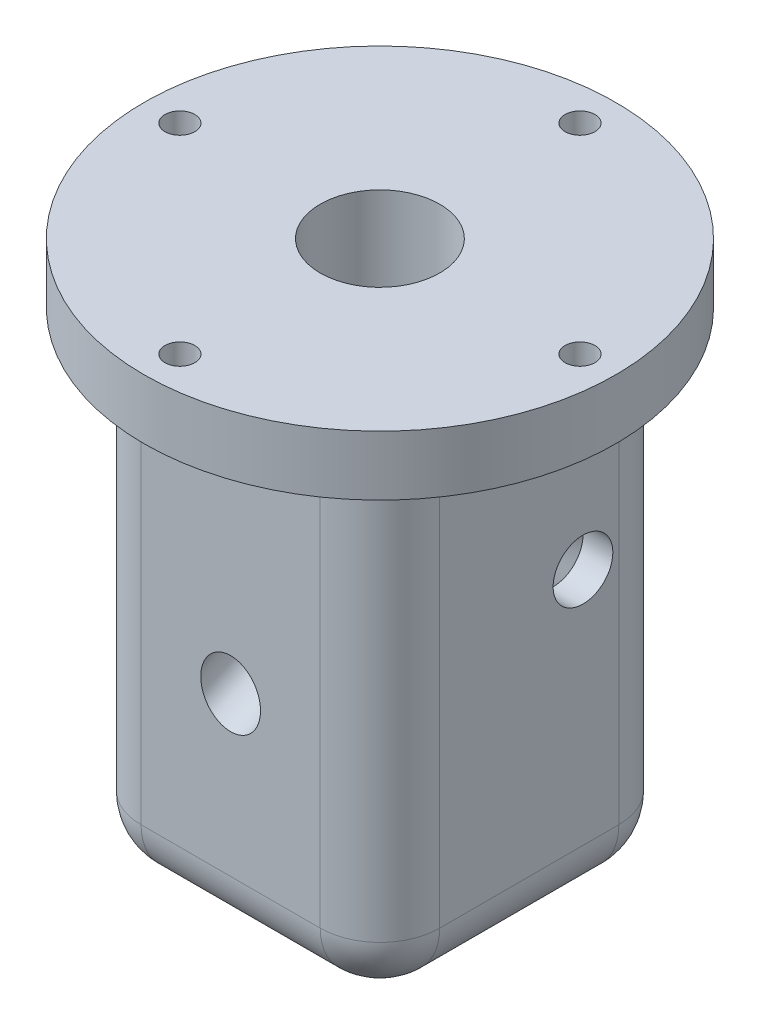
SolidWorks part; units mm, degrees
material "AISI 316 Annealed Stainless Steel Bar (SS)"
ref_plane "Front Plane" through (0, 0, 0) normal (0, 0, 1) x (1, 0, 0)
ref_plane "Top Plane" through (0, 0, 0) normal (0, 1, 0) x (1, 0, 0)
ref_plane "Right Plane" through (0, 0, 0) normal (1, 0, 0) x (0, 0, -1)
sketch "Sketch1" plane through (0, 0, 0) normal (0, 1, 0) x (1, 0, 0)
  line L1 (-15.875, 15.875) -> (15.875, 15.875)
  line L2 (-15.875, 15.875) -> (-15.875, -15.875)
  line L3 (-15.875, -15.875) -> (15.875, -15.875)
  line L4 (15.875, 15.875) -> (15.875, -15.875)
  line L5 (-15.875, 15.875) -> (15.875, -15.875) construction
  line L6 (-15.875, -15.875) -> (15.875, 15.875) construction
  point P0 (0, 0)
  dimension "D1" = 31.75
  dimension "D2" = 31.75
extrude "Stock" add sketch "Sketch1" along normal blind 50.8
sketch "Sketch5" plane through (0, 50.8, 0) normal (0, 1, 0) x (1, 0, 0)
  point P0 (0, 0)
hole_wizard "SP TAP" positions "Sketch5" profile "Sketch6" hole size "50 UNM" standard "ANSI Inch"
sketch "Sketch6" plane through (0, 50.8, 0) normal (1, 0, 0) x (0, 0, 1)
  line L0 (0, 0) -> (0, 36.8355)
  line L1 (0, 36.8355) -> (6.35, 33.02)
  line L2 (6.35, 33.02) -> (6.35, 0)
  line L5 (6.35, 0) -> (0, 0)
  line L10 (0, 36.8355) -> (-6.35, 33.02) construction
  line L11 (0, -6.35) -> (0, 107.95) construction
  dimension "Hole Dia." = 12.7
  dimension "Hole Depth" = 33.02
  dimension "Drill Angle" = 118
sketch "Sketch7" plane through (0, 0, 0) normal (0, 0, 1) x (1, 0, 0)
  line L0 (0, 17.41) -> (-34.9329, 17.41) construction
  line L1 (-34.9329, 17.41) -> (37.6053, 17.41) construction
  line L2 (37.6053, 17.41) -> (0, 17.41) construction
  line L3 (0, 17.41) -> (0, 34.2083) construction
  line L4 (0, 34.2083) -> (0, -2.3153) construction
  dimension "D1" = 17.41
ref_plane "Plane1" through (0, 3.1095, 6.6684) normal (0, 0.4226, 0.9063) x (1, 0, 0)
ref_plane "Plane2" through (0, 3.1095, -6.6684) normal (0, 0.4226, -0.9063) x (1, 0, 0)
ref_plane "Plane3" through (0, -14.0657, 30.1639) normal (0, 0.4226, -0.9063) x (1, 0, 0)
ref_plane "Plane4" through (0, -14.0657, -30.1639) normal (0, 0.4226, 0.9063) x (1, 0, 0)
sketch "Sketch9" plane through (0, -14.0657, -30.1639) normal (0, 0.4226, 0.9063) x (1, 0, 0)
  point P0 (0, 21.9666)
hole_wizard "#47 (0.0785) GOx Orfice" positions "Sketch9" profile "Sketch11" hole size "#47" standard "ANSI Inch" end condition up to next
sketch "Sketch11" plane through (0, 5.8428, -39.4474) normal (1, 0, 0) x (0, 0.9063, -0.4226)
  line L0 (0, 0) -> (0, 36.519)
  line L1 (0, 36.519) -> (0.9969, 36.519)
  line L2 (0.9969, 36.519) -> (0.9969, 0.635)
  line L3 (0.9969, 0.635) -> (1.632, 0)
  line L5 (1.632, 0) -> (0, 0)
  line L6 (-0.9969, 0.635) -> (-1.632, 0) construction
  line L11 (0, -6.35) -> (0, 107.95) construction
  dimension "Thru Hole Dia." = 1.9939
  dimension "Thru Hole Depth" = 36.519
  dimension "Near C'Sink Dia." = 3.2639
  dimension "Near C'Sink Angle" = 90
mirror "Second GOx Orfice" about plane through (0, 0, 0) normal (0, 0, 1) of "#47 (0.0785) GOx Orfice"
sketch "Centerline Fuel" plane through (15.875, 0, 0) normal (1, 0, 0) x (0, 0, -1)
  line L0 (0, 50.8) -> (0, 0) construction
  line L1 (-15.875, 50.8) -> (15.875, 50.8) construction
sketch "Kerosene Orfice Position" plane through (15.875, 0, 0) normal (1, 0, 0) x (0, 0, -1)
  line L0 (0, 0) -> (0, 25.4) construction
  line L1 (0, 50.8) -> (0, 0) construction
  line L2 (0, 25.4) -> (5.715, 25.4) construction
  dimension "D1" = 25.4
  dimension "D2" = 5.715
sketch "Sketch23" plane through (15.875, 0, 0) normal (1, 0, 0) x (0, 0, -1)
  point P0 (5.715, 25.4)
hole_wizard "#65 (0.035) Diameter Hole2" positions "Sketch23" profile "Sketch24" hole size "#65" standard "ANSI Inch" end condition up to next
sketch "Sketch24" plane through (15.875, 25.4, -5.715) normal (0, 1, 0) x (0, 0, -1)
  line L0 (0, 0) -> (0, 13.1071)
  line L1 (0, 13.1071) -> (0.4445, 13.1071)
  line L2 (0.4445, 13.1071) -> (0.4445, 0)
  line L5 (0.4445, 0) -> (0, 0)
  line L11 (0, -6.35) -> (0, 107.95) construction
  dimension "Thru Hole Dia." = 0.889
  dimension "Thru Hole Depth" = 13.1071
sketch "Sketch25" plane through (0, 0, 0) normal (0, -1, 0) x (-1, 0, 0)
  line L1 (15.875, 15.875) -> (-15.875, 15.875)
  line L2 (15.875, 15.875) -> (15.875, -15.875)
  line L3 (15.875, -15.875) -> (-15.875, -15.875)
  line L4 (-15.875, 15.875) -> (-15.875, -15.875)
  line L5 (0, -15.875) -> (0, 15.875) construction
  line L6 (15.875, 0) -> (-15.875, 0) construction
  point P0 (0, 0)
extrude "Boss-Extrude1" add sketch "Sketch25" along normal blind 6.35
sketch "Sketch27" plane through (0, -6.35, 0) normal (0, -1, 0) x (-1, 0, 0)
  point P0 (0, 0)
hole_wizard "M14 Tapped Hole1" positions "Sketch27" profile "Sketch29" tap size "M14" standard "ISO"
sketch "Sketch29" plane through (0, -6.35, 0) normal (1, 0, 0) x (0, 0, -1)
  line L0 (0, 0) -> (0, 22.6552)
  line L1 (0, 22.6552) -> (6, 19.05)
  line L2 (6, 19.05) -> (6, 1.025)
  line L3 (6, 1.025) -> (7.025, 0)
  line L5 (7.025, 0) -> (0, 0)
  line L6 (-6, 1.025) -> (-7.025, 0) construction
  line L10 (0, 22.6552) -> (-6, 19.05) construction
  line L11 (0, -6.35) -> (0, 107.95) construction
  dimension "Tap Drill Dia." = 12
  dimension "Tap Drill Depth" = 19.05
  dimension "Near C'Sink Dia." = 14.05
  dimension "Near C'Sink Angle" = 90
  dimension "Drill Angle" = 118
cosmetic thread "Hole Thread1" parameters "D1"=19.05, "D2"=14
sketch "Sketch30" plane through (0, -6.35, 0) normal (0, -1, 0) x (-1, 0, 0)
  circle A0 centre (0, 0) radius 6.0198
  dimension "D1" = 12.0396
extrude "Cut-Extrude1" cut sketch "Sketch30" against normal through all
sketch "Sketch31" plane through (0, 50.8, 0) normal (0, 1, 0) x (1, 0, 0)
  line L1 (-15.875, -15.875) -> (15.875, -15.875)
  line L2 (-15.875, -15.875) -> (-15.875, 15.875)
  line L3 (-15.875, 15.875) -> (15.875, 15.875)
  line L4 (15.875, -15.875) -> (15.875, 15.875)
  line L5 (0, 15.875) -> (0, -15.875) construction
  line L6 (-15.875, 0) -> (15.875, 0) construction
  circle A0 centre (0, 0) radius 21.2725 construction
  circle A1 centre (21.2725, 0) radius 3.5687 construction
  circle A2 centre (0, 0) radius 25.0825
  circle A3 centre (21.2725, 0) radius 1.5875
  circle A7 centre (0, -21.2725) radius 1.5875
  circle A8 centre (-21.2725, 0) radius 1.5875
  circle A9 centre (0, 21.2725) radius 1.5875
  point P22 (1.5875, 1.5875)
  point P23 (0, 0)
  dimension "D1" = 5.3975
  dimension "D2" = 3.81
  dimension "D3" = 3.175
  dimension "D4" = 7.1374
  dimension "D5" = 4
extrude "Boss-Extrude2" add sketch "Sketch31" against normal blind 6.35
sketch "Sketch33" plane through (15.875, 0, 0) normal (1, 0, 0) x (0, 0, -1)
  point P0 (5.715, 25.4)
hole_wizard "1/4 (0.25) Diameter Hole1" positions "Sketch33" profile "Sketch34" hole size "1/4" standard "ANSI Inch"
sketch "Sketch34" plane through (15.875, 25.4, -5.715) normal (0, 1, 0) x (0, 0, -1)
  line L0 (0, 0) -> (0, 5.0827)
  line L1 (0, 5.0827) -> (3.175, 3.175)
  line L2 (3.175, 3.175) -> (3.175, 0)
  line L5 (3.175, 0) -> (0, 0)
  line L10 (0, 5.0827) -> (-3.175, 3.175) construction
  line L11 (0, -6.35) -> (0, 107.95) construction
  dimension "Hole Dia." = 6.35
  dimension "Hole Depth" = 3.175
  dimension "Drill Angle" = 118
sketch "Sketch35" plane through (0, 0, 0) normal (1, 0, 0) x (0, 0, -1)
  line L0 (6.35, 21.2764) -> (15.875, 21.2764) construction
  line L1 (15.875, 44.45) -> (15.875, -6.35) construction
  line L2 (15.875, 21.2764) -> (15.875, 16.8348) construction
  line L3 (15.875, 15.7348) -> (15.875, 17.9348) construction
  line L4 (15.875, 16.8348) -> (6.35, 21.2764) construction
  line L5 (15.875, 19.0556) -> (11.1125, 19.0556) construction
  line L6 (11.1125, 19.0556) -> (11.4997, 15.3718)
  line L7 (11.4997, 15.3718) -> (19.7602, 11.5199)
  line L8 (19.7602, 11.5199) -> (21.102, 14.3974)
  line L9 (15.875, 16.8348) -> (21.102, 14.3974)
  line L10 (11.1125, 19.0556) -> (15.875, 16.8348)
  dimension "D2" = 59
  dimension "D1" = 4.7625
  dimension "D3" = 3.175
  dimension "D4" = 5.2548
revolve "Cut-Revolve1" cut sketch "Sketch35" angle 360 about L4
mirror "Mirror1" about plane through (0, 0, 0) normal (0, 0, 1) of "Cut-Revolve1"
fillet "Fillet2" radius 6.35 4 edges at (-15.875, 19.05, 15.875) (15.875, 19.05, 15.875) (15.875, 19.05, -15.875) (-15.875, 19.05, -15.875)
fillet "Fillet3" radius 6.35 8 edges at (14.0151, -6.35, -14.0151) (0, -6.35, -15.875) (-14.0151, -6.35, -14.0151) (-15.875, -6.35, 0) (-14.0151, -6.35, 14.0151) (0, -6.35, 15.875) (14.0151, -6.35, 14.0151) (15.875, -6.35, 0)
fillet "Fillet4" radius 1.5875 8 edges at (14.0151, 44.45, -14.0151) (15.875, 44.45, 0) (14.0151, 44.45, 14.0151) (0, 44.45, 15.875) (-14.0151, 44.45, 14.0151) (-15.875, 44.45, 0) (-14.0151, 44.45, -14.0151) (0, 44.45, -15.875)
